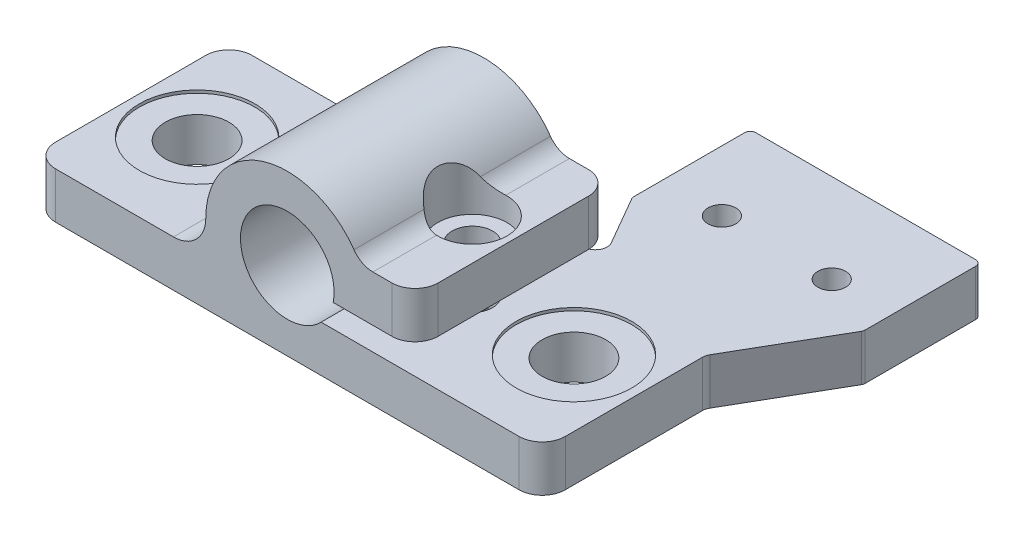
SolidWorks part; units mm, degrees
ref_plane "Front Plane" through (0, 0, 0) normal (0, 0, 1) x (1, 0, 0)
ref_plane "Top Plane" through (0, 0, 0) normal (0, 1, 0) x (1, 0, 0)
ref_plane "Right Plane" through (0, 0, 0) normal (1, 0, 0) x (0, 0, -1)
sketch "Sketch1" plane through (0, 0, 0) normal (0, 0, 1) x (1, 0, 0)
  line L0 (11.05, 4) -> (3.9702, 4)
  line L1 (-22.05, 2) -> (-9.85, 2)
  line L2 (-22.05, 2) -> (-22.05, -2)
  line L3 (-22.05, -2) -> (22.05, -2)
  line L4 (22.05, 2) -> (22.05, -2)
  line L5 (2.9262, 2) -> (22.05, 2)
  line L6 (6.2819, 8) -> (11.05, 8)
  line L7 (11.05, 8) -> (11.05, 4)
  line L9 (-9.2509, 17.8613) -> (11.05, 17.8613) construction
  arc A0 (3.9702, 4) -> (2.9262, 2) centre (0, 4.8) ccw
  arc A2 (-7.05, 4.8) -> (-9.85, 2) centre (-9.85, 4.8) cw
  arc A4 (6.2819, 8) -> (-7.05, 4.8) centre (0, 4.8) ccw
  point P5 (-22.05, 0)
  point P16 (0, -2)
  dimension "D3" = 8.1
  dimension "D5" = 2.75
  dimension "D4" = 3
  dimension "D1" = 4
  dimension "D6" = 2
  dimension "D7" = 7
  dimension "D8" = 10
  dimension "D9" = 11
extrude "Boss-Extrude1" add sketch "Sketch1" along normal mid plane 17
sketch "Sketch2" plane through (0, 2, 0) normal (0, 1, 0) x (1, 0, 0)
  line L0 (0, 8.5) -> (0, -8.5) construction
  line L1 (-7.05, -8.5) -> (6.2819, -8.5) construction
  line L2 (22.05, -8.5) -> (22.05, 8.5) construction
  circle A0 centre (16.3, 0) radius 2.75
  circle A1 centre (-16.3, 0) radius 2.75
  circle A2 centre (16.3, 0) radius 5
  circle A3 centre (-16.3, 0) radius 5
  dimension "D1" = 5.5
  dimension "D2" = 10
  dimension "D3" = 5.75
extrude "Cut-Extrude1" cut sketch "Sketch2" against normal through all and the other way up to surface (2 mm away) contours A0 | A1 region at (16.3, 2, 0) region at (-16.3, 2, 0) other way up to face at (7.5101, 4, 0)
extrude "Cut-Extrude2" cut sketch "Sketch2<3>" against normal offset from surface 3.75 and the other way up to surface (2 mm away) up to face at (0, -2, 0) other way up to face at (7.5101, 4, 0)
sketch "Sketch2<3>" plane through (0, 2, 0) normal (0, 1, 0) x (1, 0, 0) same geometry as "Sketch2"
ref_plane "Plane1" through (0, 11.85, 0) normal (0, 1, 0) x (1, 0, 0)
sketch "Sketch3" plane through (0, 11.85, 0) normal (0, 1, 0) x (1, 0, 0)
  line L0 (3.9702, 8.5) -> (11.05, 8.5) construction
  circle A0 centre (7.5101, 0) radius 3
  circle A1 centre (7.5101, 0) radius 1.75
  point P5 (7.5101, 8.5)
  dimension "D1" = 6
  dimension "D2" = 3.5
extrude "Cut-Extrude3" cut sketch "Sketch3" against normal through all contours A1 region at (7.5101, 11.85, 0)
extrude "Cut-Extrude4" cut sketch "Sketch3<3>" against normal offset from surface (5.85 mm away) 2 contours A1 | A0 A1 region at (4.595, 11.85, 0) region at (7.5101, 11.85, 0) up to face at (8.3676, 8, 0) offset beyond the face yes
sketch "Sketch3<3>" plane through (0, 11.85, 0) normal (0, 1, 0) x (1, 0, 0) same geometry as "Sketch3"
fillet "Fillet1" radius 2 3 edges at (22.05, 0, 8.5) (-22.05, 0, -8.5) (-22.05, 0, 8.5)
fillet "Fillet2" radius 2 4 edges at (11.05, 6, -8.5) (11.05, 6, 8.5) (6.2819, 8, 5.6185) (6.2819, 8, -5.6185)
sketch "Sketch4" plane through (0, -2, 0) normal (0, -1, 0) x (1, 0, 0)
  line L1 (10.7721, 0) -> (9.1411, 2.825)
  line L2 (9.1411, 2.825) -> (5.8791, 2.825)
  line L3 (5.8791, 2.825) -> (4.2481, 0)
  line L4 (4.2481, 0) -> (5.8791, -2.825)
  line L5 (5.8791, -2.825) -> (9.1411, -2.825)
  line L6 (9.1411, -2.825) -> (10.7721, 0)
  circle A0 centre (7.5101, 0) radius 2.825 construction
  dimension "D1" = 5.65
extrude "Cut-Extrude5" cut sketch "Sketch4" against normal blind 2
sketch "Sketch5" plane through (0, 2, 0) normal (0, 1, 0) x (1, 0, 0)
  line L0 (22.05, 8.5) -> (2.9262, 8.5) construction
  line L2 (27.05, 14.3) -> (27.05, 24.5)
  line L3 (27.05, 24.5) -> (7.05, 24.5)
  line L4 (7.05, 14.3) -> (7.05, 24.5)
  line L5 (27.05, 14.3) -> (22.05, 5.6397)
  line L6 (22.05, -6.5) -> (22.05, 8.5) construction
  line L7 (7.05, 14.3) -> (10.3986, 8.5)
  line L8 (22.05, 8.5) -> (10.3986, 8.5)
  line L9 (22.05, 5.6397) -> (22.05, 8.5)
  line L10 (4.05, -8.5) -> (4.05, 8.5) construction
  line L11 (21.8, 16.8) -> (12.3, 16.8) construction
  circle A0 centre (21.8, 16.8) radius 1.2
  circle A1 centre (12.3, 16.8) radius 1.2
  point P15 (17.05, 16.8)
  point P16 (17.05, 24.5)
  dimension "D7" = 9.5
  dimension "D9" = 2.4
  dimension "D1" = 10.2
  dimension "D2" = 20
  dimension "D3" = 16
  dimension "D4" = 60
  dimension "D5" = 60
  dimension "D6" = 3
  dimension "D8" = 7.7
extrude "Boss-Extrude2" add sketch "Sketch5" against normal up to surface (4 mm away) up to face at (7.5101, -2, 0)
fillet "Fillet3" radius 1 2 edges at (22.05, 0, -5.6397) (10.3986, 0, -8.5)
fillet "Fillet4" radius 0.5 4 edges at (7.05, 0, -24.5) (27.05, 0, -24.5) (7.05, 0, -14.3) (27.05, 0, -14.3)
